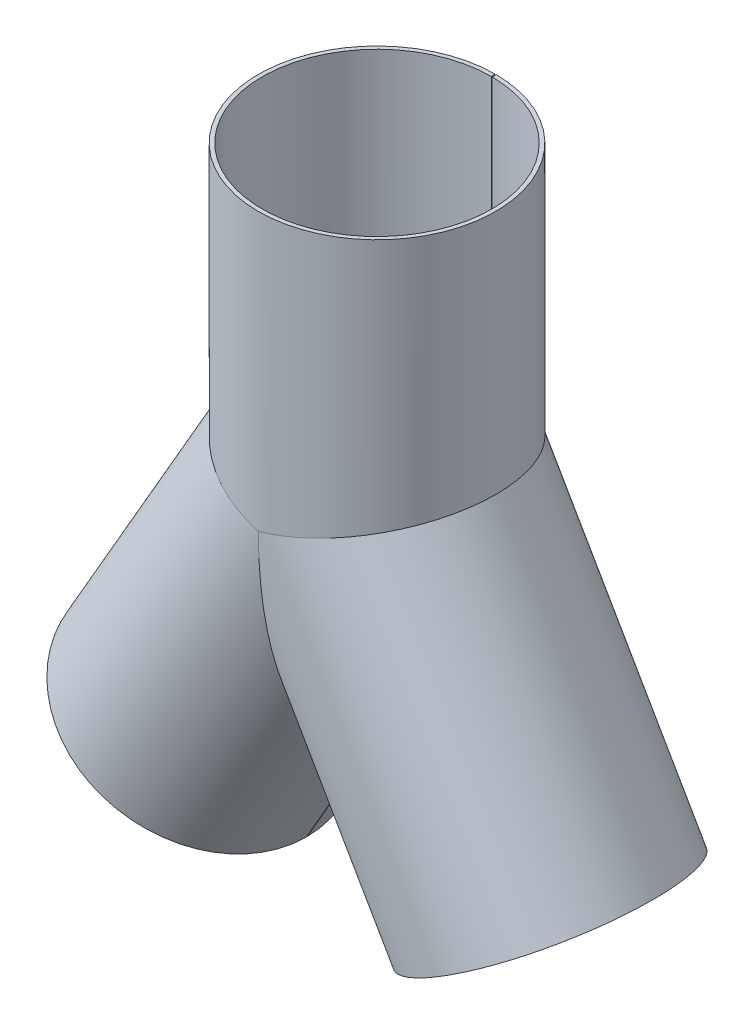
SolidWorks part; units mm, degrees
ref_plane "前视基准面" through (0, 0, 0) normal (0, 0, 1) x (1, 0, 0)
ref_plane "上视基准面" through (0, 0, 0) normal (0, 1, 0) x (1, 0, 0)
ref_plane "右视基准面" through (0, 0, 0) normal (1, 0, 0) x (0, 0, -1)
sketch "草图1" plane through (0, 0, 0) normal (0, 0, 1) x (1, 0, 0)
  line L0 (0, 280) -> (0, 0)
  line L1 (0, 0) -> (-175, -303.1089) construction
  line L2 (0, 0) -> (175, -303.1089) construction
  line L3 (0, 0) -> (0, -303.1089) construction
  line L4 (71.077, -363.1089) -> (278.923, -243.1089) construction
  line L5 (0, 0) -> (-278.923, 0) construction
  line L6 (0, 0) -> (-278.923, 74.7372) construction
  line L7 (-71.077, -363.1089) -> (-278.923, -243.1089) construction
  line L8 (0, 280) -> (0, 284) construction
  line L9 (-120, 0) -> (120, 0) construction
  line L10 (0, 0) -> (278.923, 74.7372) construction
  dimension "β" = 60
  dimension "h" = 280
  dimension "d" = 240
  dimension "l" = 350
  dimension "β/4" = 15
  dimension "t" = 4
sketch "草图2" plane through (0, 0, 0) normal (0, 1, 0) x (1, 0, 0)
  line L0 (0, 0) -> (0, 120) construction
  circle A0 centre (0, 0) radius 120
extrude "拉伸-薄壁1" add sketch "草图2" along normal up to vertex (280 mm away) thin up to point (0, 280, 0) thin type one direction reverse wall 4
ref_plane "基准面1" through (175, -303.1089, 0) normal (0.5, -0.866, 0) x (0.866, 0.5, 0)
sketch "草图3" plane through (175, -303.1089, 0) normal (0.5, -0.866, 0) x (0.866, 0.5, 0)
  circle A0 centre (0, 0) radius 120
extrude "拉伸-薄壁2" add sketch "草图3" against normal up to vertex (350 mm away) separate body thin up to point (0, 0, 0) thin type one direction reverse wall 4
sketch "草图4" plane through (0, 0, 0) normal (0, 0, 1) x (1, 0, 0)
  line L0 (-278.923, 74.7372) -> (278.923, -74.7372)
extrude "切除-拉伸3" cut sketch "草图4" against normal through all and the other way through all flip side to cut
sketch "草图5" plane through (0, 0, 0) normal (0, 0, 1) x (1, 0, 0)
  line L0 (278.923, 74.7372) -> (-278.923, -74.7372)
extrude "切除-拉伸4" cut sketch "草图5" against normal through all and the other way through all
extrude "切除-拉伸5" cut sketch "草图5<2>" against normal through all and the other way through all flip side to cut
sketch "草图5<2>" plane through (0, 0, 0) normal (0, 0, 1) x (1, 0, 0) same geometry as "草图5"
sketch "草图6" plane through (0, 0, 0) normal (0, 0, 1) x (1, 0, 0)
  line L0 (0, 280) -> (0, -363.1089)
extrude "切除-拉伸6" cut sketch "草图6" against normal through all and the other way through all flip side to cut
extrude "切除-拉伸-薄壁2" cut sketch "草图1" against normal through all thin thin type mid plane wall 1
sketch "草图7" plane through (175, -303.1089, 0) normal (0.5, -0.866, 0) x (0.866, 0.5, 0)
  line L0 (0, 0) -> (-120, 0)
extrude "切除-拉伸-薄壁3" cut sketch "草图7" against normal through all thin thin type mid plane wall 1
mirror "镜向1" about plane through (0, 0, 0) normal (1, 0, 0) of bodies 112 102
equation "\"β/4@草图1\" = \"β@草图1\"/4"
equation "\"D5@拉伸-薄壁1\" = \"t@草图1\""
equation "\"D5@拉伸-薄壁2\" = \"t@草图1\""
